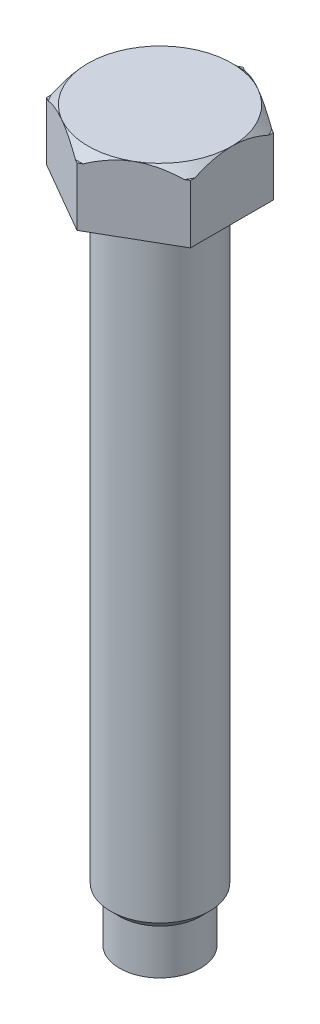
SolidWorks part; units mm, degrees
ref_plane "Front Plane" through (0, 0, 0) normal (0, 0, 1) x (1, 0, 0)
ref_plane "Top Plane" through (0, 0, 0) normal (0, 1, 0) x (1, 0, 0)
ref_plane "Right Plane" through (0, 0, 0) normal (1, 0, 0) x (0, 0, -1)
sketch "Sketch1" plane through (0, 0, 0) normal (0, 1, 0) x (1, 0, 0)
  circle A0 centre (0, 0) radius 5.5
  dimension "D1" = 11
extrude "Extrude1" add sketch "Sketch1" along normal blind 73
sketch "Sketch2" plane through (0, 73, 0) normal (0, 1, 0) x (1, 0, 0)
  line L0 (0, -6.05) -> (0, 6.05) construction
  line L1 (8, -4.6188) -> (8, 4.6188)
  line L2 (8, 4.6188) -> (0, 9.2376)
  line L3 (0, 9.2376) -> (-8, 4.6188)
  line L4 (-8, 4.6188) -> (-8, -4.6188)
  line L5 (-8, -4.6188) -> (0, -9.2376)
  line L6 (0, -9.2376) -> (8, -4.6188)
  circle A0 centre (0, 0) radius 8 construction
  dimension "D1" = 16
  dimension "D2" = 60
extrude "Extrude2" add sketch "Sketch2" along normal blind 8
sketch "Sketch3" plane through (0, 73, 0) normal (0, -1, 0) x (1, 0, 0)
  circle A0 centre (0, 0) radius 14.1167
  circle A1 centre (0, 0) radius 7
  dimension "D1" = 14
extrude "Extrude3" cut sketch "Sketch3" against normal blind 0.5
sketch "Sketch4" plane through (0, 0, 0) normal (0, -1, 0) x (1, 0, 0)
  circle A0 centre (0, 0) radius 19.6937
  circle A1 centre (0, 0) radius 4.5
  dimension "D1" = 9
extrude "Extrude4" cut sketch "Sketch4" against normal blind 5
chamfer "Chamfer1" distance 1 angle 45 1 edges at (0, 5, -5.5)
sketch "Sketch5" plane through (0, 81, 0) normal (0, 1, 0) x (1, 0, 0)
  circle A0 centre (0, 0) radius 8
  circle A1 centre (0, 0) radius 25.5889
  dimension "D1" = 16
extrude "Extrude5" cut sketch "Sketch5" against normal blind 1
chamfer "Chamfer2" distance 1 angle 45 6 edges at (-6.9282, 80, 4) (0, 80, 8) (6.9282, 80, 4) (6.9282, 80, -4) (0, 80, -8) (-6.9282, 80, -4)
